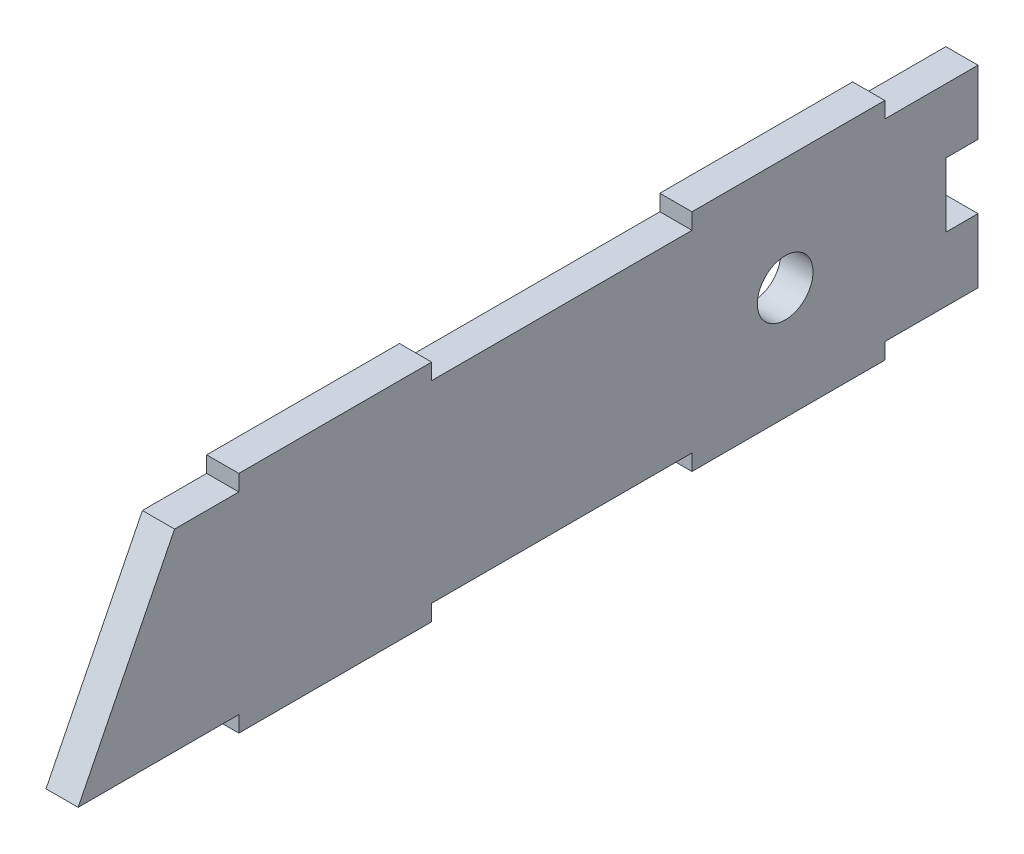
SolidWorks part; units mm, degrees
ref_plane "Front Plane" through (0, 0, 0) normal (0, 0, 1) x (1, 0, 0)
ref_plane "Top Plane" through (0, 0, 0) normal (0, 1, 0) x (1, 0, 0)
ref_plane "Right Plane" through (0, 0, 0) normal (1, 0, 0) x (0, 0, -1)
sketch "Sketch1" plane through (0, 0, 0) normal (1, 0, 0) x (0, 0, -1)
  line L1 (-177.8, -38.1) -> (177.8, -38.1)
  line L2 (-177.8, -38.1) -> (-177.8, 38.1)
  line L3 (-177.8, 38.1) -> (177.8, 38.1)
  line L4 (177.8, -38.1) -> (177.8, 38.1)
  line L5 (-177.8, -38.1) -> (177.8, 38.1) construction
  line L6 (-177.8, 38.1) -> (177.8, -38.1) construction
  point P0 (0, 0)
  dimension "D1" = 355.6
  dimension "D2" = 76.2
extrude "Boss-Extrude1" add sketch "Sketch1" along normal blind 12.7
sketch "Sketch2" plane through (12.7, 0, 0) normal (1, 0, 0) x (0, 0, -1)
  line L0 (-177.8, -38.1) -> (-139.7, 38.1)
  line L1 (177.8, 38.1) -> (-177.8, 38.1) construction
  dimension "D1" = 38.1
extrude "Cut-Extrude1" cut sketch "Sketch2" against normal through all and the other way through all
sketch "Sketch3" plane through (0, 0, 0) normal (-1, 0, 0) x (0, 0, 1)
  line L0 (177.8, -38.1) -> (-177.8, -38.1) construction
  line L1 (-140.97, -38.1) -> (-64.77, -38.1)
  line L2 (-140.97, -38.1) -> (-140.97, -44.45)
  line L3 (-140.97, -44.45) -> (-64.77, -44.45)
  line L4 (-64.77, -38.1) -> (-64.77, -44.45)
  line L5 (-177.8, -38.1) -> (-177.8, 38.1) construction
  line L6 (38.1, -38.1) -> (114.3, -38.1)
  line L7 (38.1, -38.1) -> (38.1, -44.45)
  line L8 (38.1, -44.45) -> (114.3, -44.45)
  line L9 (114.3, -38.1) -> (114.3, -44.45)
  line L10 (-177.8, 38.1) -> (139.7, 38.1) construction
  line L11 (-140.97, 38.1) -> (-64.77, 38.1)
  line L12 (-140.97, 38.1) -> (-140.97, 44.45)
  line L13 (-140.97, 44.45) -> (-64.77, 44.45)
  line L14 (-64.77, 38.1) -> (-64.77, 44.45)
  line L16 (38.1, 38.1) -> (114.3, 38.1)
  line L17 (38.1, 38.1) -> (38.1, 44.45)
  line L18 (38.1, 44.45) -> (114.3, 44.45)
  line L19 (114.3, 38.1) -> (114.3, 44.45)
  dimension "D1" = 76.2
  dimension "D2" = 6.35
  dimension "D3" = 76.2
  dimension "D4" = 6.35
  dimension "D5" = 36.83
  dimension "D6" = 215.9
  dimension "D7" = 76.2
  dimension "D8" = 6.35
  dimension "D9" = 6.35
  dimension "D10" = 76.2
extrude "Boss-Extrude2" add sketch "Sketch3" against normal blind 12.7
sketch "Sketch4" plane through (0, 0, 0) normal (-1, 0, 0) x (0, 0, 1)
  line L0 (-177.8, -38.1) -> (-177.8, 38.1) construction
  line L1 (-177.8, 12.7) -> (-165.1, 12.7)
  line L2 (-177.8, 12.7) -> (-177.8, -12.7)
  line L3 (-177.8, -12.7) -> (-165.1, -12.7)
  line L4 (-165.1, 12.7) -> (-165.1, -12.7)
  line L5 (-140.97, -38.1) -> (-177.8, -38.1) construction
  line L6 (-177.8, 38.1) -> (-140.97, 38.1) construction
  dimension "D1" = 25.4
  dimension "D2" = 25.4
  dimension "D3" = 12.7
extrude "Cut-Extrude2" cut sketch "Sketch4" against normal through all
sketch "Sketch5" plane through (0, 0, 0) normal (-1, 0, 0) x (0, 0, 1)
  line L0 (-165.1, -12.7) -> (-165.1, 12.7) construction
  line L1 (-140.97, -38.1) -> (-177.8, -38.1) construction
  circle A0 centre (-101.6, 0) radius 11
  dimension "D1" = 63.5
  dimension "D3" = 22
  dimension "D2" = 38.1
extrude "Cut-Extrude3" cut sketch "Sketch5" against normal through all
